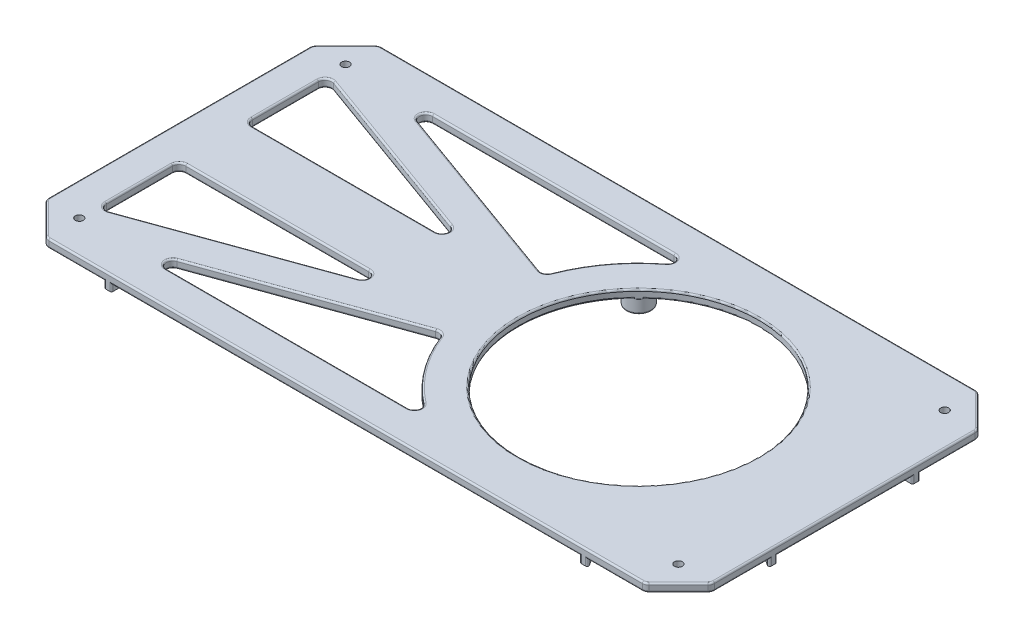
SolidWorks part; units mm, degrees
ref_plane "Front Plane" through (0, 0, 0) normal (0, 0, 1) x (1, 0, 0)
ref_plane "Top Plane" through (0, 0, 0) normal (0, 1, 0) x (1, 0, 0)
ref_plane "Right Plane" through (0, 0, 0) normal (1, 0, 0) x (0, 0, -1)
sketch "Sketch1" plane through (0, 0, 0) normal (0, 1, 0) x (1, 0, 0)
  line L0 (-42.8795, -50) -> (-18.9309, -50) construction
  line L1 (0, 0) -> (200, 0)
  line L2 (0, 0) -> (0, -100)
  line L3 (0, -100) -> (200, -100)
  line L4 (200, 0) -> (200, -100)
  line L5 (100, -119.9176) -> (100, -112.0024) construction
  line L6 (10, -15.3158) -> (10, -40)
  line L7 (24.7249, -10) -> (115.2844, -10)
  line L8 (10, -40) -> (78.3752, -40)
  line L9 (10, -10) -> (93.1001, -40) construction
  line L10 (10, -15.3158) -> (78.3752, -40)
  line L11 (24.7249, -10) -> (94.455, -35.1733)
  line L12 (24.7249, -10) -> (10, -10) construction
  line L13 (10, -10) -> (10, -15.3158) construction
  line L14 (78.3752, -40) -> (93.1001, -40) construction
  line L15 (24.7249, -90) -> (94.455, -64.8267)
  line L16 (24.7249, -90) -> (115.2844, -90)
  line L17 (10, -84.6842) -> (78.3752, -60)
  line L18 (10, -60) -> (78.3752, -60)
  line L19 (10, -84.6842) -> (10, -60)
  circle A0 centre (138, -50) radius 36
  arc A1 (115.2844, -10) -> (94.455, -35.1733) centre (138, -50) ccw
  circle A2 centre (10, -90) radius 1.2 construction
  circle A3 centre (10, -10) radius 1.2 construction
  arc A4 (94.455, -35.1733) -> (93.1001, -40) centre (138, -50) ccw construction
  circle A5 centre (190, -90) radius 1.2 construction
  arc A6 (115.2844, -90) -> (94.455, -64.8267) centre (138, -50) cw
  circle A8 centre (190, -10) radius 1.2 construction
  circle A10 centre (10, -90) radius 1.2
  circle A11 centre (10, -10) radius 1.2
  circle A13 centre (190, -90) radius 1.2
  circle A16 centre (190, -10) radius 1.2
  point P8 (100, -100)
  point P10 (0, -50)
  dimension "D3" = 72
  dimension "D5" = 5
  dimension "D7" = 10
  dimension "D1" = 200
  dimension "D2" = 100
  dimension "D4" = 62
  dimension "D6" = 10
  dimension "D8" = 40
  dimension "D9" = 10
  dimension "D10" = 10
extrude "Boss-Extrude1" add sketch "Sketch1" along normal blind 2.5
chamfer "Chamfer1" distance 10 angle 45 4 edges at (200, 1.25, 0) (200, 1.25, 100) (0, 1.25, 100) (0, 1.25, 0)
sketch "Sketch3" plane through (0, 0, 0) normal (0, -1, 0) x (1, 0, 0)
  circle A0 centre (178.081, 30.6143) radius 2.5 construction
  circle A1 centre (110.023, 21.9343) radius 2.5 construction
  circle A2 centre (178.081, 69.3857) radius 2.5 construction
  circle A3 centre (110.023, 78.0657) radius 2.5 construction
  circle A4 centre (178.081, 30.6143) radius 2.5 construction
  circle A5 centre (110.023, 21.9343) radius 2.5 construction
  circle A6 centre (178.081, 69.3857) radius 2.5 construction
  circle A7 centre (110.023, 78.0657) radius 2.5 construction
  circle A8 centre (110.023, 78.0657) radius 3.75
  circle A9 centre (178.081, 69.3857) radius 3.75
  circle A10 centre (178.081, 30.6143) radius 3.75
  circle A11 centre (110.023, 21.9343) radius 3.75
  dimension "D1" = 7.5
  dimension "D2" = 7.5
  dimension "D3" = 7.5
  dimension "D4" = 7.5
sketch "Sketch6" plane through (0, 0, 0) normal (0, -1, 0) x (1, 0, 0)
  circle A2 centre (138, 50) radius 36 construction
  circle A3 centre (138, 50) radius 36 construction
sketch "Sketch7" plane through (0, 0, 0) normal (0, -1, 0) x (1, 0, 0)
  line L0 (158.2222, 21.4332) -> (188.2, 42.6543) construction
  line L1 (188.2, 57.3457) -> (158.2222, 78.5668) construction
  line L2 (158.2222, 21.4332) -> (188.2, 42.6543) construction
  line L3 (188.2, 57.3457) -> (158.2222, 78.5668) construction
  line L4 (158.8, 20.617) -> (188.7778, 41.8381)
  line L5 (188.7778, 58.1619) -> (158.8, 79.383)
  line L13 (95.9429, 50) -> (70.6151, 50) construction
  arc A1 (188.2, 42.6543) -> (192, 50) centre (183, 50) ccw construction
  arc A2 (192, 50) -> (188.2, 57.3457) centre (183, 50) ccw construction
  arc A4 (188.2, 42.6543) -> (192, 50) centre (183, 50) ccw construction
  arc A5 (192, 50) -> (188.2, 57.3457) centre (183, 50) ccw construction
  arc A8 (188.7778, 41.8381) -> (193, 50) centre (183, 50) ccw
  arc A9 (193, 50) -> (188.7778, 58.1619) centre (183, 50) ccw
  arc A15 (158.8, 79.383) -> (158.8, 20.617) centre (138, 50) ccw
  dimension "D1" = 1
extrude "Cut-Extrude1" cut sketch "Sketch7" against normal blind 1
extrude "Boss-Extrude2" add sketch "Sketch3" along normal blind 4
sketch "Sketch8" plane through (0, 0, 0) normal (0, -1, 0) x (1, 0, 0)
  line L0 (29.6667, 2.3486) -> (29.6667, 0.5) construction
  line L1 (29.1667, 0) -> (27.9343, 0) construction
  line L2 (27.5182, 0.7774) -> (28.7506, 2.626) construction
  line L3 (171.2494, 2.626) -> (172.4818, 0.7774) construction
  line L4 (172.0657, 0) -> (170.8333, 0) construction
  line L5 (170.3333, 0.5) -> (170.3333, 2.3486) construction
  line L6 (199.2226, 27.5182) -> (197.374, 28.7506) construction
  line L7 (197.6514, 29.6667) -> (199.5, 29.6667) construction
  line L8 (200, 29.1667) -> (200, 27.9343) construction
  line L9 (199.5, 70.3333) -> (197.6514, 70.3333) construction
  line L10 (197.374, 71.2494) -> (199.2226, 72.4818) construction
  line L11 (200, 72.0657) -> (200, 70.8333) construction
  line L12 (172.4818, 99.2226) -> (171.2494, 97.374) construction
  line L13 (170.3333, 97.6514) -> (170.3333, 99.5) construction
  line L14 (170.8333, 100) -> (172.0657, 100) construction
  line L15 (0.5, 29.6667) -> (2.3486, 29.6667) construction
  line L16 (2.626, 28.7506) -> (0.7774, 27.5182) construction
  line L17 (0, 27.9343) -> (0, 29.1667) construction
  line L18 (0.7774, 72.4818) -> (2.626, 71.2494) construction
  line L19 (2.3486, 70.3333) -> (0.5, 70.3333) construction
  line L20 (0, 70.8333) -> (0, 72.0657) construction
  line L21 (29.6667, 99.5) -> (29.6667, 97.6514) construction
  line L22 (28.7506, 97.374) -> (27.5182, 99.2226) construction
  line L23 (27.9343, 100) -> (29.1667, 100) construction
  line L24 (29.6667, 2.3486) -> (29.6667, 0.5)
  line L25 (29.1667, 0) -> (27.9343, 0)
  line L26 (27.5182, 0.7774) -> (28.7506, 2.626)
  line L27 (171.2494, 2.626) -> (172.4818, 0.7774)
  line L28 (172.0657, 0) -> (170.8333, 0)
  line L29 (170.3333, 0.5) -> (170.3333, 2.3486)
  line L30 (199.2226, 27.5182) -> (197.374, 28.7506)
  line L31 (197.6514, 29.6667) -> (199.5, 29.6667)
  line L32 (200, 29.1667) -> (200, 27.9343)
  line L33 (199.5, 70.3333) -> (197.6514, 70.3333)
  line L34 (197.374, 71.2494) -> (199.2226, 72.4818)
  line L35 (200, 72.0657) -> (200, 70.8333)
  line L36 (172.4818, 99.2226) -> (171.2494, 97.374)
  line L37 (170.3333, 97.6514) -> (170.3333, 99.5)
  line L38 (170.8333, 100) -> (172.0657, 100)
  line L39 (0.5, 29.6667) -> (2.3486, 29.6667)
  line L40 (2.626, 28.7506) -> (0.7774, 27.5182)
  line L41 (0, 27.9343) -> (0, 29.1667)
  line L42 (0.7774, 72.4818) -> (2.626, 71.2494)
  line L43 (2.3486, 70.3333) -> (0.5, 70.3333)
  line L44 (0, 70.8333) -> (0, 72.0657)
  line L45 (29.6667, 99.5) -> (29.6667, 97.6514)
  line L46 (28.7506, 97.374) -> (27.5182, 99.2226)
  line L47 (27.9343, 100) -> (29.1667, 100)
  arc A0 (29.1667, 0) -> (29.6667, 0.5) centre (29.1667, 0.5) ccw construction
  arc A1 (27.5182, 0.7774) -> (27.9343, 0) centre (27.9343, 0.5) ccw construction
  arc A2 (29.6667, 2.3486) -> (28.7506, 2.626) centre (29.1667, 2.3486) ccw construction
  arc A3 (172.0657, 0) -> (172.4818, 0.7774) centre (172.0657, 0.5) ccw construction
  arc A4 (170.3333, 0.5) -> (170.8333, 0) centre (170.8333, 0.5) ccw construction
  arc A5 (171.2494, 2.626) -> (170.3333, 2.3486) centre (170.8333, 2.3486) ccw construction
  arc A6 (197.6514, 29.6667) -> (197.374, 28.7506) centre (197.6514, 29.1667) ccw construction
  arc A7 (200, 29.1667) -> (199.5, 29.6667) centre (199.5, 29.1667) ccw construction
  arc A8 (199.2226, 27.5182) -> (200, 27.9343) centre (199.5, 27.9343) ccw construction
  arc A9 (197.374, 71.2494) -> (197.6514, 70.3333) centre (197.6514, 70.8333) ccw construction
  arc A10 (200, 72.0657) -> (199.2226, 72.4818) centre (199.5, 72.0657) ccw construction
  arc A11 (199.5, 70.3333) -> (200, 70.8333) centre (199.5, 70.8333) ccw construction
  arc A12 (170.3333, 97.6514) -> (171.2494, 97.374) centre (170.8333, 97.6514) ccw construction
  arc A13 (170.8333, 100) -> (170.3333, 99.5) centre (170.8333, 99.5) ccw construction
  arc A14 (172.4818, 99.2226) -> (172.0657, 100) centre (172.0657, 99.5) ccw construction
  arc A15 (2.626, 28.7506) -> (2.3486, 29.6667) centre (2.3486, 29.1667) ccw construction
  arc A16 (0, 27.9343) -> (0.7774, 27.5182) centre (0.5, 27.9343) ccw construction
  arc A17 (0.5, 29.6667) -> (0, 29.1667) centre (0.5, 29.1667) ccw construction
  arc A18 (2.3486, 70.3333) -> (2.626, 71.2494) centre (2.3486, 70.8333) ccw construction
  arc A19 (0, 70.8333) -> (0.5, 70.3333) centre (0.5, 70.8333) ccw construction
  arc A20 (0.7774, 72.4818) -> (0, 72.0657) centre (0.5, 72.0657) ccw construction
  arc A21 (28.7506, 97.374) -> (29.6667, 97.6514) centre (29.1667, 97.6514) ccw construction
  arc A22 (27.9343, 100) -> (27.5182, 99.2226) centre (27.9343, 99.5) ccw construction
  arc A23 (29.6667, 99.5) -> (29.1667, 100) centre (29.1667, 99.5) ccw construction
  arc A24 (29.1667, 0) -> (29.6667, 0.5) centre (29.1667, 0.5) ccw
  arc A25 (27.5182, 0.7774) -> (27.9343, 0) centre (27.9343, 0.5) ccw
  arc A26 (29.6667, 2.3486) -> (28.7506, 2.626) centre (29.1667, 2.3486) ccw
  arc A27 (172.0657, 0) -> (172.4818, 0.7774) centre (172.0657, 0.5) ccw
  arc A28 (170.3333, 0.5) -> (170.8333, 0) centre (170.8333, 0.5) ccw
  arc A29 (171.2494, 2.626) -> (170.3333, 2.3486) centre (170.8333, 2.3486) ccw
  arc A30 (197.6514, 29.6667) -> (197.374, 28.7506) centre (197.6514, 29.1667) ccw
  arc A31 (200, 29.1667) -> (199.5, 29.6667) centre (199.5, 29.1667) ccw
  arc A32 (199.2226, 27.5182) -> (200, 27.9343) centre (199.5, 27.9343) ccw
  arc A33 (197.374, 71.2494) -> (197.6514, 70.3333) centre (197.6514, 70.8333) ccw
  arc A34 (200, 72.0657) -> (199.2226, 72.4818) centre (199.5, 72.0657) ccw
  arc A35 (199.5, 70.3333) -> (200, 70.8333) centre (199.5, 70.8333) ccw
  arc A36 (170.3333, 97.6514) -> (171.2494, 97.374) centre (170.8333, 97.6514) ccw
  arc A37 (170.8333, 100) -> (170.3333, 99.5) centre (170.8333, 99.5) ccw
  arc A38 (172.4818, 99.2226) -> (172.0657, 100) centre (172.0657, 99.5) ccw
  arc A39 (2.626, 28.7506) -> (2.3486, 29.6667) centre (2.3486, 29.1667) ccw
  arc A40 (0, 27.9343) -> (0.7774, 27.5182) centre (0.5, 27.9343) ccw
  arc A41 (0.5, 29.6667) -> (0, 29.1667) centre (0.5, 29.1667) ccw
  arc A42 (2.3486, 70.3333) -> (2.626, 71.2494) centre (2.3486, 70.8333) ccw
  arc A43 (0, 70.8333) -> (0.5, 70.3333) centre (0.5, 70.8333) ccw
  arc A44 (0.7774, 72.4818) -> (0, 72.0657) centre (0.5, 72.0657) ccw
  arc A45 (28.7506, 97.374) -> (29.6667, 97.6514) centre (29.1667, 97.6514) ccw
  arc A46 (27.9343, 100) -> (27.5182, 99.2226) centre (27.9343, 99.5) ccw
  arc A47 (29.6667, 99.5) -> (29.1667, 100) centre (29.1667, 99.5) ccw
extrude "Boss-Extrude3" add sketch "Sketch8" along normal blind 2
fillet "Fillet1" radius 2 20 edges at (200, 1.25, 10) (190, 1.25, 0) (190, 1.25, 100) (200, 1.25, 90) (10, 1.25, 100) (0, 1.25, 90) (10, 1.25, 0) (0, 1.25, 10) (24.7249, 1.25, 90) (115.2844, 1.25, 90) (94.455, 1.25, 64.8267) (10, 1.25, 60) (78.3752, 1.25, 60) (10, 1.25, 84.6842) (10, 1.25, 40) (78.3752, 1.25, 40) (94.455, 1.25, 35.1733) (115.2844, 1.25, 10) (24.7249, 1.25, 10) (10, 1.25, 15.3158)
fillet "Fillet2" radius 0.5 102 edges at (135.4333, 0, 14.0916) (135.4333, 0, 85.9084) (183.4972, 0, 38.1) (183.4972, 0, 61.9) (102, 0, 50) (166.6507, 0, 26.1745) (166.6507, 0, 73.8255) (193, 0, 50) (110.023, -4, 18.1843) (110.023, -4, 74.3157) (178.081, -4, 26.8643) (178.081, -4, 65.6357) (138, 2.5, 86) (174, 1, 50) (189.9369, 2.5, 0.1522) (195, 2.5, 5) (199.8478, 2.5, 10.0631) (200, 2.5, 50) (199.8478, 2.5, 89.9369) (195, 2.5, 95) (189.9369, 2.5, 99.8478) (100, 2.5, 100) (10.0631, 2.5, 99.8478) (5, 2.5, 95) (0.1522, 2.5, 89.9369) (0, 2.5, 50) (0.1522, 2.5, 10.0631) (5, 2.5, 5) (10.0631, 2.5, 0.1522) (189.9369, 0, 0.1522) (195, 0, 5) (199.8478, 0, 10.0631) (200, 0, 19.3813) (200, 0, 80.6187) (199.8478, 0, 89.9369) (195, 0, 95) (189.9369, 0, 99.8478) (180.6187, 0, 100) (19.3813, 0, 100) (10.0631, 0, 99.8478) (5, 0, 95) (0.1522, 0, 89.9369) (0, 0, 80.6187) (0, 0, 19.3813) (0.1522, 0, 10.0631) (5, 0, 5) (10.0631, 0, 0.1522) (100, 2.5, 0) (180.6187, 0, 0) (19.3813, 0, 0) (34.1848, 0, 11.6553) (72.4146, 0, 10) (110.5672, 0, 11.3545) (101.1606, 0, 22.4526) (94.0869, 0, 34.4357) (10.5858, 0, 39.4142) (10, 0, 28.0821) (10.8507, 0, 16.5274) (40.1517, 0, 26.2009) (68.9153, 0, 38.3447) (10.8507, 0, 83.4726) (10, 0, 71.9179) (10.5858, 0, 60.5858) (39.4726, 0, 60) (68.9153, 0, 61.6553) (34.1848, 0, 88.3447) (64.0278, 0, 75.8113) (94.0869, 0, 65.5643) (101.1606, 0, 77.5474) (110.5672, 0, 88.6455) (34.1848, 2.5, 11.6553) (72.4146, 2.5, 10) (110.5672, 2.5, 11.3545) (101.1606, 2.5, 22.4526) (94.0869, 2.5, 34.4357) (10.5858, 2.5, 39.4142) (10, 2.5, 28.0821) (10.8507, 2.5, 16.5274) (40.1517, 2.5, 26.2009) (68.9153, 2.5, 38.3447) (10.8507, 2.5, 83.4726) (10, 2.5, 71.9179) (10.5858, 2.5, 60.5858) (39.4726, 2.5, 60) (68.9153, 2.5, 61.6553) (34.1848, 2.5, 88.3447) (64.0278, 2.5, 75.8113) (94.0869, 2.5, 65.5643) (101.1606, 2.5, 77.5474) (110.5672, 2.5, 88.6455) (64.0278, 0, 24.1887) (39.4726, 0, 40) (40.1517, 0, 73.7991) (72.4146, 0, 90) (64.0278, 2.5, 24.1887) (39.4726, 2.5, 40) (40.1517, 2.5, 73.7991) (72.4146, 2.5, 90) (0, 0, 50) (100, 0, 0) (100, 0, 100) (200, 0, 50)
